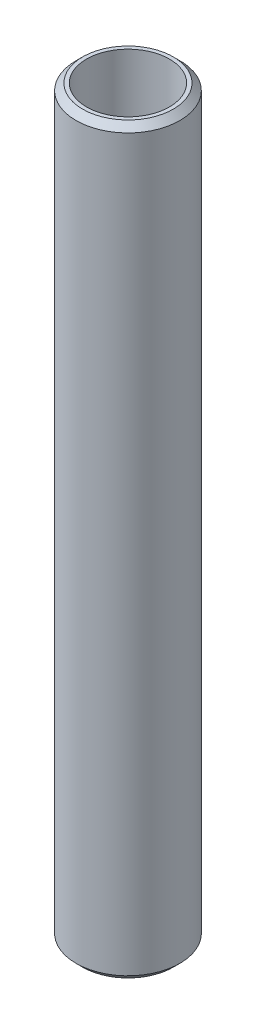
SolidWorks part; units mm, degrees
ref_plane "Front Plane" through (0, 0, 0) normal (0, 0, 1) x (1, 0, 0)
ref_plane "Top Plane" through (0, 0, 0) normal (0, 1, 0) x (1, 0, 0)
ref_plane "Right Plane" through (0, 0, 0) normal (1, 0, 0) x (0, 0, -1)
sketch "Sketch1" plane through (0, 0, 0) normal (0, 1, 0) x (1, 0, 0)
  circle A0 centre (0, 0) radius 37.5
  dimension "SHAFT_OD" = 75
extrude "Boss-Extrude1" add sketch "Sketch1" along normal blind 536.9156
sketch "Sketch2" plane through (0, 0, 0) normal (0, 1, 0) x (1, 0, 0)
  circle A0 centre (0, 0) radius 29.9903
  dimension "BORE_D" = 59.9805
extrude "Cut-Extrude1" cut sketch "Sketch2" along normal through all
chamfer "Chamfer1" distance 4.7509 angle 45 2 edges at (0, 536.9156, 37.5) (0, 0, 37.5)
